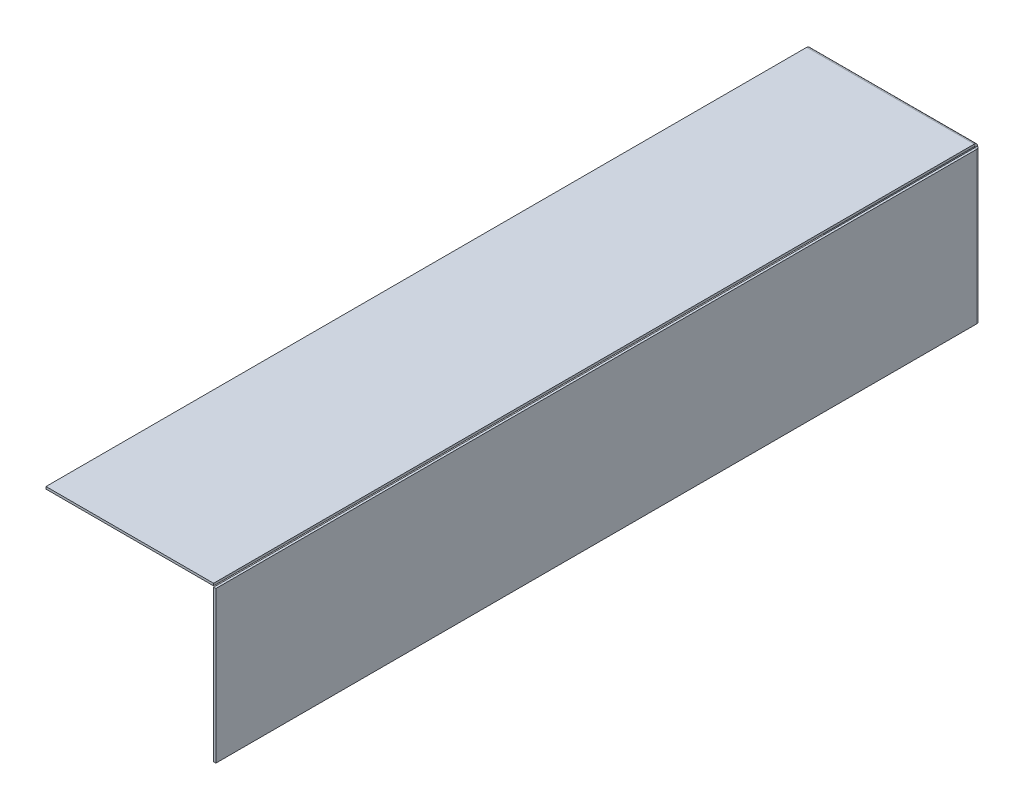
SolidWorks part; units mm, degrees
note: The reader was unsure of these and kept them because the rebuilt part matched: flange length of "Kenar-Flanş2", "Kenar-Flanş4".
ref_plane "Ön Düzlem" through (0, 0, 0) normal (0, 0, 1) x (1, 0, 0)
ref_plane "Üst Düzlem" through (0, 0, 0) normal (0, 1, 0) x (1, 0, 0)
ref_plane "Sağ Düzlem" through (0, 0, 0) normal (1, 0, 0) x (0, 0, -1)
sketch "Çizim1" plane through (0, 0, 0) normal (0, 0, 1) x (1, 0, 0)
  line L0 (0, 0) -> (0, 70)
  line L1 (140, 100) -> (30, 100)
  line L2 (140, 100) -> (140, 0)
  line L3 (140, 0) -> (0, 0)
  line L4 (0, 70) -> (30, 100)
  point P1 (0, 100)
  dimension "D1" = 140
  dimension "D2" = 100
base flange "Taban-Flanş2" sketch "Çizim1" thickness 1.5 reverse thickness direction no parameters "D1"=0.7366
edge flange "Kenar-Flanş2" sketch "Çizim34" flange angle 90 flange length 500 flange position material outside bend radius 0.7366 thickness 1.5 relief rectangular parameters "D6"=10
sketch "Çizim34" plane through (0, 100, 0) normal (0, -1, 0) x (1, 0, 0)
  line L1 (140, 0) -> (30, 0) construction
  line L2 (30, 0) -> (30, 500)
  line L3 (30, 500) -> (140, 500)
  line L4 (140, 500) -> (140, 0)
  line L5 (140, 0) -> (30, 0)
bend "KenarBükümü6" bend radius 0.7366 bend angle 90 parameters "D5"=1
edge flange "Kenar-Flanş4" sketch "Çizim40" flange angle 90 flange length 500 flange position material outside bend radius 0.7366 thickness 1.5 relief none parameters "D6"=10
sketch "Çizim40" plane through (140, 0, 0) normal (-1, 0, 0) x (0, -1, 0)
  line L1 (0, 0) -> (-99.2634, 0) construction
  line L2 (-99.2634, 0) -> (-99.2634, 500)
  line L3 (-99.2634, 500) -> (0, 500)
  line L4 (0, 500) -> (0, 0)
  line L5 (0, 0) -> (-99.2634, 0)
bend "KenarBükümü8" bend radius 0.7366 bend angle 90 parameters "D5"=2
sketch "Büküm-Çizgileri3" [suppressed] plane through (0, 0, 0) normal (0, 1, 0) x (1, 0, 0)
sketch "Sınırlandırma-Kutusu3" [suppressed] plane through (0, 0, 0) normal (0, 1, 0) x (1, 0, 0)
sheet metal parameters "Sac-Levha4" thickness 1.5 parameters "D1"=0.7366
flat pattern "Düz-Çoğaltma4" [suppressed]
sketch "Büküm-Çizgileri4" plane through (0, 0, 0) normal (0, 1, 0) x (1, 0, 0)
sketch3d "Sınırlandırma-Kutusu4" [suppressed]
  line L0 (0, 0, 0) -> (140, 0, 0) construction
  line L1 (0, 100, 0) -> (140, 100, 0) construction
  line L2 (0, 0, 0) -> (0, 100, 0) construction
  line L3 (140, 0, 0) -> (140, 100, 0) construction
sheet metal parameters "Sac-Levha6" thickness 1.5 parameters "D1"=0.7366
flat pattern "Düz-Çoğaltma4"
sketch "Büküm-Çizgileri4" plane through (0, 0, 0) normal (0, 0, 1) x (1, 0, 0)
  line L0 (140, 100.431) -> (30, 100.431) construction
  line L1 (140, 100.431) -> (30, 100.431) construction
sketch3d "Sınırlandırma-Kutusu4" [suppressed]
  line L0 (140, 600.8619, 0) -> (140, 0, 0) construction
  line L1 (0, 600.8619, 0) -> (0, 0, 0) construction
  line L2 (140, 600.8619, 0) -> (0, 600.8619, 0) construction
  line L3 (140, 0, 0) -> (0, 0, 0) construction
bend of the flat pattern "Düzleştirme TipiKenarBükümü6>1"
sheet metal parameters "Sac-Levha8" thickness 1.5 parameters "D1"=0.7366
flat pattern "Düz-Çoğaltma4"
sketch "Büküm-Çizgileri4" plane through (0, 0, 0) normal (0, 0, 1) x (1, 0, 0)
  line L0 (140, 100.431) -> (30, 100.431) construction
  line L1 (140, 100.431) -> (30, 100.431) construction
  line L2 (140.431, 0) -> (140.431, 99.2634) construction
  line L3 (140.431, 0) -> (140.431, 99.2634) construction
sketch3d "Sınırlandırma-Kutusu4" [suppressed]
  line L0 (0, 0, 0) -> (640.8619, 0, 0) construction
  line L1 (0, 600.8619, 0) -> (640.8619, 600.8619, 0) construction
  line L2 (0, 0, 0) -> (0, 600.8619, 0) construction
  line L3 (640.8619, 0, 0) -> (640.8619, 600.8619, 0) construction
bend of the flat pattern "Düzleştirme TipiKenarBükümü6>1"
bend of the flat pattern "Düzleştirme TipiKenarBükümü8>1"
